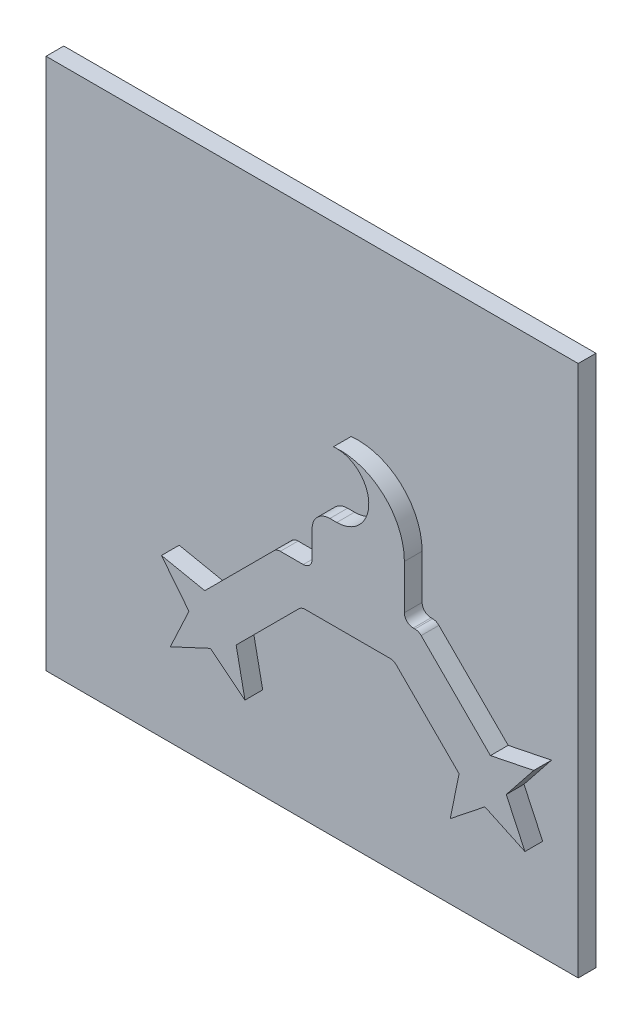
SolidWorks part; units mm, degrees
material "Obyčejná uhlíková ocel"
ref_plane "Přední rovina" through (0, 0, 0) normal (0, 0, 1) x (1, 0, 0)
ref_plane "Horní rovina" through (0, 0, 0) normal (0, 1, 0) x (1, 0, 0)
ref_plane "Pravá rovina" through (0, 0, 0) normal (1, 0, 0) x (0, 0, -1)
sketch "Skica1" plane through (0, 0, 0) normal (0, 0, 1) x (1, 0, 0)
  line L1 (0, 0) -> (300, 0)
  line L2 (0, 0) -> (0, 300)
  line L3 (0, 300) -> (300, 300)
  line L4 (300, 0) -> (300, 300)
  dimension "D1" = 300
extrude "Přidat vysunutím1" add sketch "Skica1" along normal blind 10
sketch "Skica3" plane through (0, 0, 10) normal (0, 0, 1) x (1, 0, 0)
  line L69 (0, 300) -> (0, 0) construction
  line L70 (99.4835, 93.8388) -> (138.5355, 132.8909)
  line L74 (102.6269, 67.2491) -> (117.1612, 76.1612) construction
  line L77 (221.4645, 132.8909) -> (260.5165, 93.8388)
  line L84 (242.8388, 76.1612) -> (207.4645, 111.5355)
  line L85 (203.9289, 113) -> (156.0711, 113)
  line L86 (152.5355, 111.5355) -> (117.1612, 76.1612)
  line L87 (117.1612, 76.1612) -> (122.1369, 51.7388)
  line L89 (102.6269, 67.2491) -> (80.0381, 56.7157)
  line L90 (80.0381, 56.7157) -> (90.5714, 79.3046)
  line L92 (75.0612, 98.8146) -> (99.4835, 93.8388)
  line L94 (170, 164.3553) -> (173.8947, 164.3553)
  line L96 (0, 0) -> (300, 0) construction
  line L97 (300, 0) -> (300, 300) construction
  line L98 (140, 134.3553) -> (220, 134.3553) construction
  line L99 (80.0381, 56.7157) -> (108.3223, 85) construction
  line L100 (99.4835, 93.8388) -> (117.1612, 76.1612) construction
  line L101 (90.5714, 79.3046) -> (102.6269, 67.2491) construction
  line L102 (102.6269, 67.2491) -> (122.1369, 51.7388)
  line L103 (75.0612, 98.8146) -> (90.5714, 79.3046)
  line L104 (142.0711, 134.3553) -> (155, 134.3553)
  line L105 (160, 139.3553) -> (160, 154.3553)
  line L106 (217.9289, 134.3553) -> (217, 134.3553)
  line L107 (212, 139.3553) -> (212, 164.3553)
  line L108 (180, 113) -> (180, 42.2966) construction
  line L109 (284.9388, 98.8146) -> (260.5165, 93.8388)
  line L110 (284.9388, 98.8146) -> (269.4286, 79.3046)
  line L111 (279.9619, 56.7157) -> (269.4286, 79.3046)
  line L112 (257.3731, 67.2491) -> (279.9619, 56.7157)
  line L113 (257.3731, 67.2491) -> (237.8631, 51.7388)
  line L114 (242.8388, 76.1612) -> (237.8631, 51.7388)
  arc A60 (212, 164.3553) -> (172, 200.3553) centre (175.8, 164.3553) ccw
  arc A61 (172, 200.3553) -> (173.8947, 164.3553) centre (173.8947, 182.4052) cw
  arc A63 (170, 164.3553) -> (160, 154.3553) centre (170, 154.3553) ccw
  arc A64 (217, 134.3553) -> (212, 139.3553) centre (217, 139.3553) cw
  arc A65 (217.9289, 134.3553) -> (221.4645, 132.8909) centre (217.9289, 129.3553) cw
  arc A66 (155, 134.3553) -> (160, 139.3553) centre (155, 139.3553) ccw
  arc A67 (207.4645, 111.5355) -> (203.9289, 113) centre (203.9289, 108) ccw
  arc A68 (156.0711, 113) -> (152.5355, 111.5355) centre (156.0711, 108) ccw
  arc A69 (138.5355, 132.8909) -> (142.0711, 134.3553) centre (142.0711, 129.3553) cw
  point P26 (180, 134.3553)
  point P27 (180, 113)
  point P34 (96.5992, 73.2768)
  point P46 (212, 134.3553)
  point P52 (160, 134.3553)
  point P55 (206, 113)
  point P58 (154, 113)
  dimension "D2" = 113
  dimension "D3" = 120
  dimension "D12" = 10
  dimension "D18" = 5
  dimension "D4" = 52
  dimension "D5" = 80
  dimension "D6" = 135
  dimension "D7" = 25
  dimension "D8" = 85
  dimension "D9" = 108.3223
  dimension "D10" = 40
  dimension "D11" = 140
  dimension "D13" = 20
  dimension "D14" = 8
  dimension "D15" = 30
  dimension "D16" = 36
  dimension "D17" = 40
extrude "Přidat vysunutím3" add sketch "Skica3" along normal blind 10
